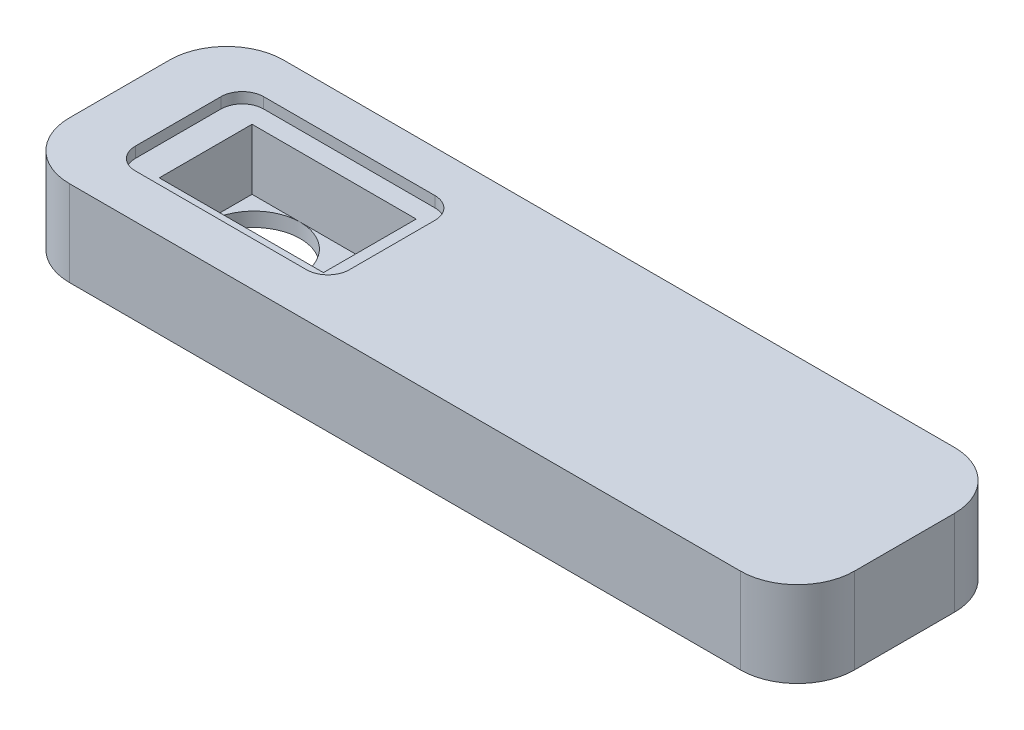
SolidWorks part; units mm, degrees
ref_plane "Front Plane" through (0, 0, 0) normal (0, 0, 1) x (1, 0, 0)
ref_plane "Top Plane" through (0, 0, 0) normal (0, 1, 0) x (1, 0, 0)
ref_plane "Right Plane" through (0, 0, 0) normal (1, 0, 0) x (0, 0, -1)
sketch "Sketch1" plane through (0, 0, 0) normal (0, 1, 0) x (1, 0, 0)
  line L1 (-46.7568, 18.1081) -> (63.2432, 18.1081)
  line L2 (-46.7568, 18.1081) -> (-46.7568, -11.8919)
  line L3 (-46.7568, -11.8919) -> (63.2432, -11.8919)
  line L4 (63.2432, 18.1081) -> (63.2432, -11.8919)
  dimension "D1" = 110
  dimension "D2" = 30
extrude "Boss-Extrude1" add sketch "Sketch1" along normal blind 12
fillet "Fillet2" radius 8 4 edges at (63.2432, 6, -18.1081) (63.2432, 6, 11.8919) (-46.7568, 6, -18.1081) (-46.7568, 6, 11.8919)
sketch "Sketch3" plane through (0, 12, 0) normal (0, 1, 0) x (1, 0, 0)
  line L0 (55.2432, 18.1081) -> (-38.7568, 18.1081) construction
  line L1 (-34.6791, 9.6081) -> (-11.6791, 9.6081)
  line L2 (-34.6791, 9.6081) -> (-34.6791, -3.3919)
  line L3 (-34.6791, -3.3919) -> (-11.6791, -3.3919)
  line L4 (-11.6791, 9.6081) -> (-11.6791, -3.3919)
  point P4 (-23.1791, 9.6081)
  dimension "D1" = 23
  dimension "D2" = 13
  dimension "D3" = 8.5
sketch "Sketch4" plane through (0, 12, 0) normal (0, 1, 0) x (1, 0, 0)
  line L0 (55.2432, 18.1081) -> (-38.7568, 18.1081) construction
  line L1 (-34.6791, 9.6081) -> (-34.6791, -3.3919) construction
  line L2 (8.2432, 18.1081) -> (8.2432, -21.5981) construction
  circle A0 centre (-27.9291, 3.1081) radius 6.5
  dimension "D1" = 15
  dimension "D2" = 6.75
extrude "Cut-Extrude1" cut sketch "Sketch4" against normal through all contours A0
extrude "Cut-Extrude2" cut sketch "Sketch3" against normal blind 10
sketch "Sketch5" plane through (0, 12, 0) normal (0, 1, 0) x (1, 0, 0)
  line L1 (-38.709, 12.2731) -> (-8.709, 12.2731)
  line L2 (-38.709, 12.2731) -> (-38.709, -5.7269)
  line L3 (-38.709, -5.7269) -> (-8.709, -5.7269)
  line L4 (-8.709, 12.2731) -> (-8.709, -5.7269)
  dimension "D1" = 30
  dimension "D2" = 18
extrude "Cut-Extrude3" cut sketch "Sketch5" against normal blind 1.5
fillet "Fillet4" radius 3 4 edges at (-38.709, 11.25, 5.7269) (-8.709, 11.25, 5.7269) (-38.709, 11.25, -12.2731) (-8.709, 11.25, -12.2731)
